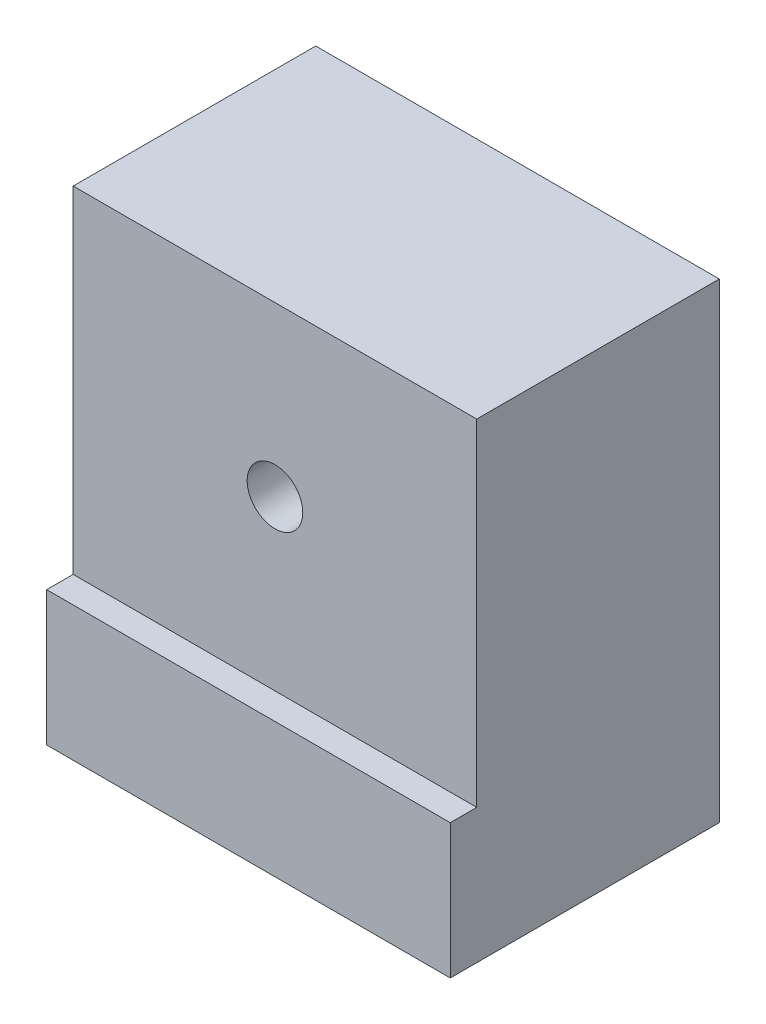
SolidWorks part; units mm, degrees
ref_plane "Front Plane" through (0, 0, 0) normal (0, 0, 1) x (1, 0, 0)
ref_plane "Top Plane" through (0, 0, 0) normal (0, 1, 0) x (1, 0, 0)
ref_plane "Right Plane" through (0, 0, 0) normal (1, 0, 0) x (0, 0, -1)
sketch "Sketch1" plane through (0, 0, 0) normal (0, 1, 0) x (1, 0, 0)
  line L1 (0, 0) -> (76.2, 0)
  line L2 (0, 0) -> (0, 50.8)
  line L3 (0, 50.8) -> (76.2, 50.8)
  line L4 (76.2, 0) -> (76.2, 50.8)
  dimension "D1" = 76.2
  dimension "D2" = 50.8
extrude "Boss-Extrude1" add sketch "Sketch1" along normal blind 88.9
sketch "Sketch2" plane through (0, 0, 0) normal (0, 0, 1) x (1, 0, 0)
  line L1 (0, 0) -> (38.1, 0)
  line L2 (0, 0) -> (0, 57.15)
  line L3 (0, 57.15) -> (38.1, 57.15)
  line L4 (38.1, 0) -> (38.1, 57.15)
  circle A0 centre (38.1, 57.15) radius 5.25
  dimension "D1" = 38.1
  dimension "D2" = 57.15
extrude "Cut-Extrude1" cut sketch "Sketch2" against normal blind 300 contours A0
sketch "Sketch3" plane through (0, 0, 0) normal (0, 0, 1) x (1, 0, 0)
  line L0 (76.2, 88.9) -> (76.2, 0) construction
  line L1 (0, 88.9) -> (76.2, 88.9)
  line L2 (0, 88.9) -> (0, 25.4)
  line L3 (0, 25.4) -> (76.2, 25.4)
  line L4 (76.2, 88.9) -> (76.2, 25.4)
  dimension "D1" = 63.5
extrude "Cut-Extrude2" cut sketch "Sketch3" against normal blind 5
sketch "Sketch4" plane through (0, 88.9, 0) normal (0, 1, 0) x (1, 0, 0)
  line L0 (76.2, 5) -> (76.2, 30.4)
  line L1 (76.2, 5) -> (76.2, 50.8) construction
  line L2 (76.2, 50.8) -> (0, 50.8) construction
  line L3 (76.2, 30.4) -> (30.4, 30.4)
  line L4 (76.2, 30.4) -> (76.2, 50.8)
  line L5 (76.2, 50.8) -> (30.4, 50.8)
  line L6 (30.4, 30.4) -> (30.4, 50.8)
  line L7 (76.2, 30.4) -> (30.4, 50.8)
  dimension "D1" = 25.4
  dimension "D2" = 20.4
  dimension "D3" = 45.8
